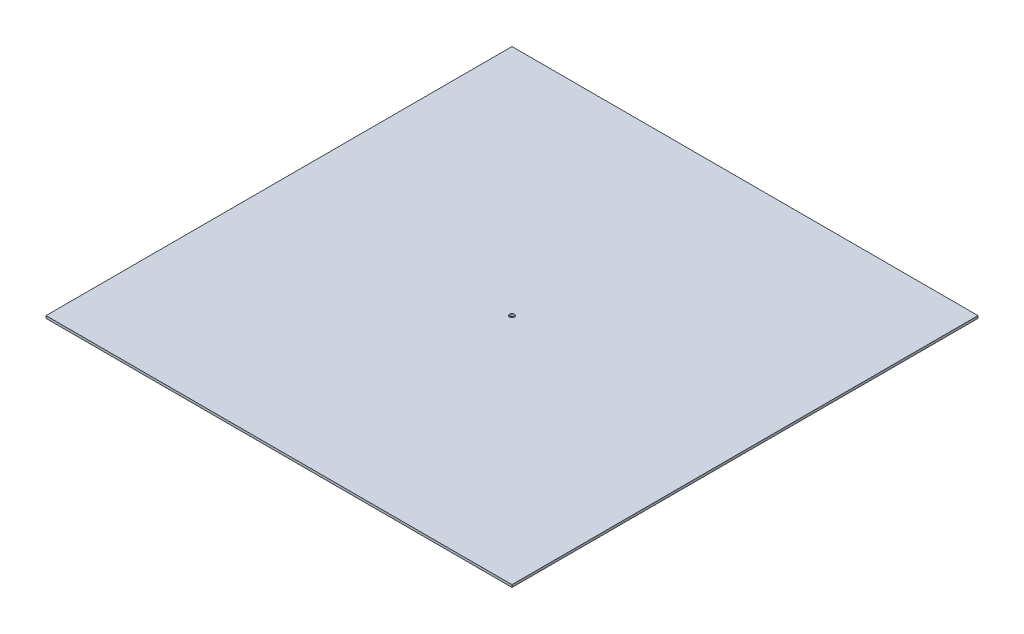
SolidWorks part; units mm, degrees
ref_plane "Front" through (0, 0, 0) normal (0, 0, 1) x (1, 0, 0)
ref_plane "Top" through (0, 0, 0) normal (0, 1, 0) x (1, 0, 0)
ref_plane "Right" through (0, 0, 0) normal (1, 0, 0) x (0, 0, -1)
sketch "Sketch1" plane through (0, 0, 0) normal (0, 1, 0) x (1, 0, 0)
  line L1 (-2413, -2413) -> (2413, -2413)
  line L2 (-2413, -2413) -> (-2413, 2413)
  line L3 (-2413, 2413) -> (2413, 2413)
  line L4 (2413, -2413) -> (2413, 2413)
  line L5 (-2413, -2413) -> (2413, 2413) construction
  line L6 (-2413, 2413) -> (2413, -2413) construction
  point P0 (0, 0)
  dimension "D1" = 4826
  dimension "D2" = 4826
extrude "Boss-Extrude1" add sketch "Sketch1" along normal blind 25.4
sketch "Sketch2" plane through (0, 0, 0) normal (0, -1, 0) x (1, 0, 0)
  circle A0 centre (0, 0) radius 25.4
  dimension "D1" = 50.8
extrude "Cut-Extrude1" cut sketch "Sketch2" against normal through all
